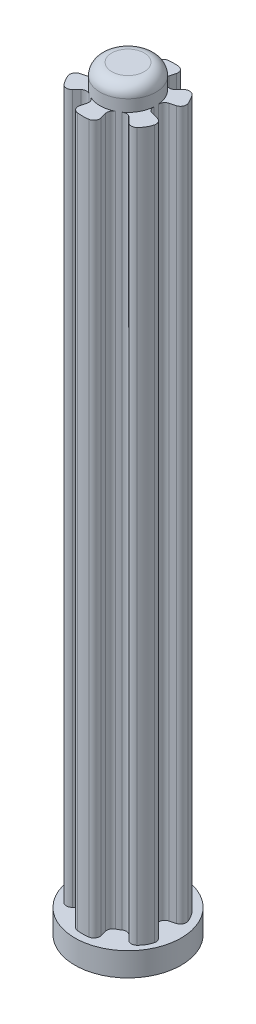
SolidWorks part; units mm, degrees
ref_plane "Front Plane" through (0, 0, 0) normal (0, 0, 1) x (1, 0, 0)
ref_plane "Top Plane" through (0, 0, 0) normal (0, 1, 0) x (1, 0, 0)
ref_plane "Right Plane" through (0, 0, 0) normal (1, 0, 0) x (0, 0, -1)
sketch "Sketch2" plane through (0, 0, 0) normal (0, 1, 0) x (1, 0, 0)
  line L0 (0, 0) -> (0.0739, 0)
  line L2 (2.3008, -0.5891) -> (3.7752, -0.9786)
  line L3 (0.0739, 0) -> (0.1042, -0.0303)
  line L4 (0, 0) -> (0.0858, -0.0446)
  line L5 (1.6802, 1.6786) -> (2.7413, 2.7388)
  line L6 (-1.6794, 1.6794) -> (-2.74, 2.74)
  line L8 (0.6147, 2.2941) -> (1.0029, 3.743)
  line L9 (-0.6147, 2.2941) -> (-1.0029, 3.743)
  line L10 (2.2941, 0.6147) -> (3.743, 1.0029)
  line L11 (0, 0) -> (0.1042, -0.0303)
  line L12 (-2.2941, 0.6147) -> (-3.743, 1.0029)
  line L13 (0.0739, 0) -> (0.0858, -0.0446)
  line L14 (-0.6147, -2.2941) -> (-1.0029, -3.743)
  line L15 (-2.2941, -0.6147) -> (-3.743, -1.0029)
  line L16 (-1.6794, -1.6794) -> (-2.74, -2.74)
  line L17 (0.6814, -2.2752) -> (1.0684, -3.7248)
  line L18 (1.7145, -1.6435) -> (2.7672, -2.6981)
  arc A0 (-2.2941, 0.6147) -> (-2.2941, -0.6147) centre (0, 0) ccw
  arc A1 (-2.74, 2.74) -> (-3.743, 1.0029) centre (0, 0) ccw
  arc A2 (1.0029, 3.743) -> (-1.0029, 3.743) centre (0, 0) ccw
  arc A3 (3.743, 1.0029) -> (2.7413, 2.7388) centre (0, 0) ccw
  arc A5 (-1.0029, -3.743) -> (1.0684, -3.7248) centre (0, 0) ccw
  arc A6 (-3.743, -1.0029) -> (-2.74, -2.74) centre (0, 0) ccw
  arc A7 (-2.74, 2.74) -> (-3.743, 1.0029) centre (0, 0) ccw
  arc A8 (1.0029, 3.743) -> (-1.0029, 3.743) centre (0, 0) ccw
  arc A9 (3.743, 1.0029) -> (2.7413, 2.7388) centre (0, 0) ccw
  arc A10 (-3.743, -1.0029) -> (-2.74, -2.74) centre (0, 0) ccw
  arc A11 (-1.0029, -3.743) -> (1.0684, -3.7248) centre (0, 0) ccw
  arc A12 (2.7672, -2.6981) -> (3.7752, -0.9786) centre (1.7753, -0.9614) ccw
  arc A13 (-0.6147, 2.2941) -> (-1.6794, 1.6794) centre (0, 0) ccw
  arc A14 (1.6802, 1.6786) -> (0.6147, 2.2941) centre (0, 0) ccw
  arc A15 (2.3008, -0.5891) -> (2.2941, 0.6147) centre (0, 0) ccw
  arc A16 (0.6814, -2.2752) -> (1.7145, -1.6435) centre (0, 0) ccw
  arc A17 (-1.6794, -1.6794) -> (-0.6147, -2.2941) centre (0, 0) ccw
  dimension "D1" = 3.875
  dimension "D2" = 2.375
extrude "Boss-Extrude1" add sketch "Sketch2" along normal blind 60 contours L16 A17 L14 A5 L17 A16 L18 A12 L2 A15 L10 A3 L5 A14 L8 A2 L9 A13 L6 A1 L12 A0 L15 A6 L11 L13 L4 L0 L3 region at (0.0225, 0, 0.0171)
sketch "Sketch3" plane through (0, 0, 0) normal (0, -1, 0) x (1, 0, 0)
  circle A0 centre (0, 0) radius 4.5
  dimension "D1" = 9
extrude "Boss-Extrude2" add sketch "Sketch3" along normal blind 2
sketch "Sketch4" plane through (0, 60, 0) normal (0, 1, 0) x (1, 0, 0)
  circle A0 centre (0, 0) radius 2.375
  dimension "D1" = 4.75
extrude "Boss-Extrude3" add sketch "Sketch4" along normal blind 2
fillet "Fillet1" radius 0.5 24 edges at (-2.74, 30, -2.74) (-1.6794, 30, -1.6794) (-0.6147, 30, -2.2941) (-1.0029, 30, -3.743) (1.0029, 30, -3.743) (0.6147, 30, -2.2941) (1.6802, 30, -1.6786) (2.7413, 30, -2.7388) (3.743, 30, -1.0029) (2.2941, 30, -0.6147) (2.3008, 30, 0.5891) (3.7752, 30, 0.9786) (2.7672, 30, 2.6981) (1.7145, 30, 1.6435) (0.6814, 30, 2.2752) (-1.6794, 30, 1.6794) (-2.2941, 30, 0.6147) (-2.2941, 30, -0.6147) (-0.6147, 30, 2.2941) (-3.743, 30, -1.0029) (-3.743, 30, 1.0029) (-2.74, 30, 2.74) (-1.0029, 30, 3.743) (1.0684, 30, 3.7248)
sketch "Sketch6" plane through (0, -2, 0) normal (0, -1, 0) x (1, 0, 0)
  circle A0 centre (0, 0) radius 1
  dimension "D1" = 2
extrude "Cut-Extrude4" cut sketch "Sketch6" against normal blind 0.5 draft 50
fillet "Fillet2" radius 1 1 edges at (0, 62, 2.375)
